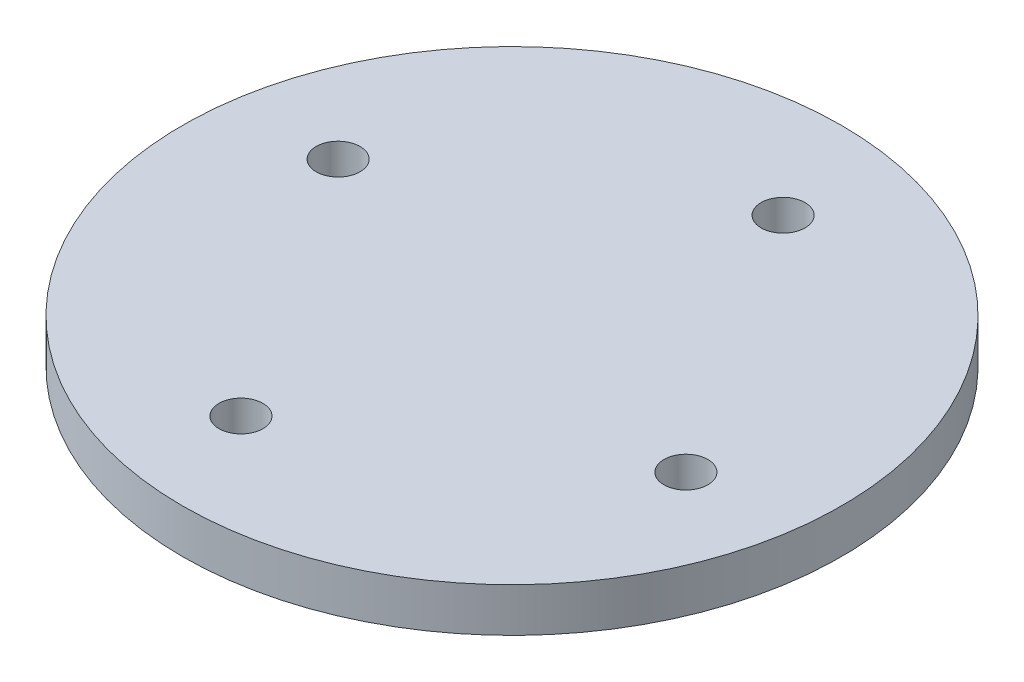
SolidWorks part; units mm, degrees
ref_plane "Front Plane" through (0, 0, 0) normal (0, 0, 1) x (1, 0, 0)
ref_plane "Top Plane" through (0, 0, 0) normal (0, 1, 0) x (1, 0, 0)
ref_plane "Right Plane" through (0, 0, 0) normal (1, 0, 0) x (0, 0, -1)
sketch "Sketch1" plane through (0, 0, 0) normal (0, 1, 0) x (1, 0, 0)
  circle A0 centre (0, 0) radius 15
  circle A1 centre (0, 0) radius 10.365
  circle A2 centre (2.2116, 10.1263) radius 1
  circle A3 centre (10.1263, -2.2116) radius 1
  circle A4 centre (-2.2116, -10.1263) radius 1
  circle A5 centre (-10.1263, 2.2116) radius 1
  point P15 (0, 0)
  dimension "D1" = 20.73
  dimension "30" = 30
  dimension "D2" = 2
  dimension "D3" = 4
extrude "Boss-Extrude1" add sketch "Sketch1" along normal blind 2 contours A0 A5 A1 A2 A3 A4 | A5 A1 A4 A3 A2 region at (-14.5757, 0, 0) region at (0, 0, 0)
